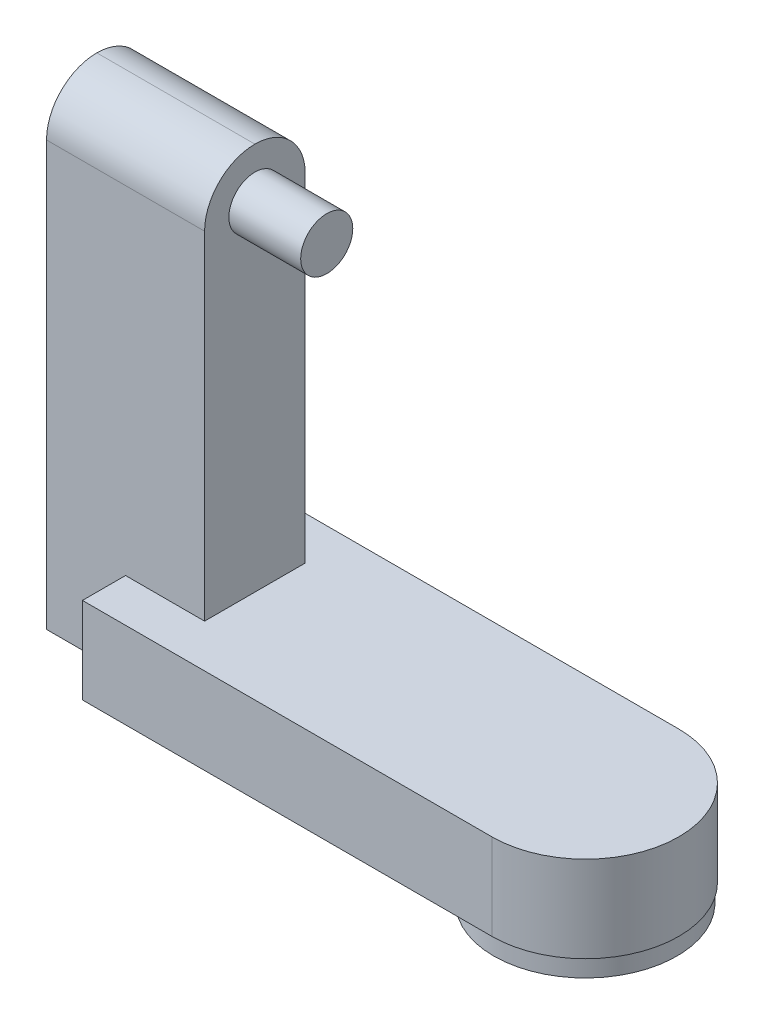
SolidWorks part; units mm, degrees
ref_plane "Front Plane" through (0, 0, 0) normal (0, 0, 1) x (1, 0, 0)
ref_plane "Top Plane" through (0, 0, 0) normal (0, 1, 0) x (1, 0, 0)
ref_plane "Right Plane" through (0, 0, 0) normal (1, 0, 0) x (0, 0, -1)
sketch "Sketch1" plane through (0, 0, 0) normal (0, 1, 0) x (1, 0, 0)
  line L1 (-114, 26) -> (0, 26)
  line L2 (-114, 26) -> (-114, -26)
  line L3 (-114, -26) -> (0, -26)
  arc A1 (0, -26) -> (0, 26) centre (0, 0) ccw
  point P3 (-46.1648, 0.8875)
  dimension "D3" = 114
  dimension "D2" = 52
extrude "Boss-Extrude2" add sketch "Sketch1" along normal blind 24
sketch "Sketch2" plane through (0, 0, 0) normal (0, -1, 0) x (1, 0, 0)
  circle A0 centre (0, 0) radius 25.5
extrude "Boss-Extrude3" add sketch "Sketch2" along normal blind 5
sketch "Sketch3" plane through (0, 0, 0) normal (0, 1, 0) x (1, 0, 0)
  line L0 (-114, 26) -> (-114, -26) construction
  line L1 (-136, 14) -> (-92, 14)
  line L2 (-136, 14) -> (-136, -14)
  line L3 (-136, -14) -> (-92, -14)
  line L4 (-92, 14) -> (-92, -14)
  line L5 (-136, 14) -> (-92, -14) construction
  line L6 (-136, -14) -> (-92, 14) construction
  point P0 (-114, 0)
  dimension "D1" = 44
  dimension "D2" = 28
extrude "Boss-Extrude4" add sketch "Sketch3" along normal blind 132
fillet "Fillet2" radius 14 1 edges at (-114, 132, 14) type face fillet first side face at (-114, 132, 0) second side face at (-114, 52, 14)
fillet "Fillet5" radius 14 1 edges at (-114, 132, -14) type face fillet first side face at (-114, 132, -7) second side face at (-114, 52, -14)
ref_plane "Plane1" through (-92, 0, 0) normal (1, 0, 0) x (0, 0, -1)
sketch "Sketch4" plane through (-92, 0, 0) normal (1, 0, 0) x (0, 0, -1)
  circle A0 centre (0, 118) radius 7.25
extrude "Boss-Extrude5" add sketch "Sketch4" along normal blind 20
ref_point "Point3"
ref_point "Point1"
ref_point "Point2"
ref_axis "Axis2" through (-157.75, 118, 0) along (1, 0, 0)
ref_axis "Axis1" through (0, 152.1942, 0) along (0, -1, 0)
sketch "Sketch5" plane through (0, -5, 0) normal (0, -1, 0) x (1, 0, 0)
  line L0 (0, 0) -> (0, 25.5) construction
  circle A0 centre (0, 0) radius 25.5 construction
ref_plane "Plane3" through (0, 0, 0) normal (0, 0, -1) x (-1, 0, 0)
ref_plane "Plane5" through (0, 0, 0) normal (1, 0, 0) x (0, 0, -1)
ref_plane "Plane6" through (0, 118, 0) normal (0, 1, 0) x (1, 0, 0)
sketch "Sketch6" plane through (0, 118, -118) normal (0, 1, 0) x (-1, 0, 0)
  line L2 (157.75, 118) -> (-100.6335, 118) construction
  circle A0 centre (0, 118) radius 28.4537 construction
